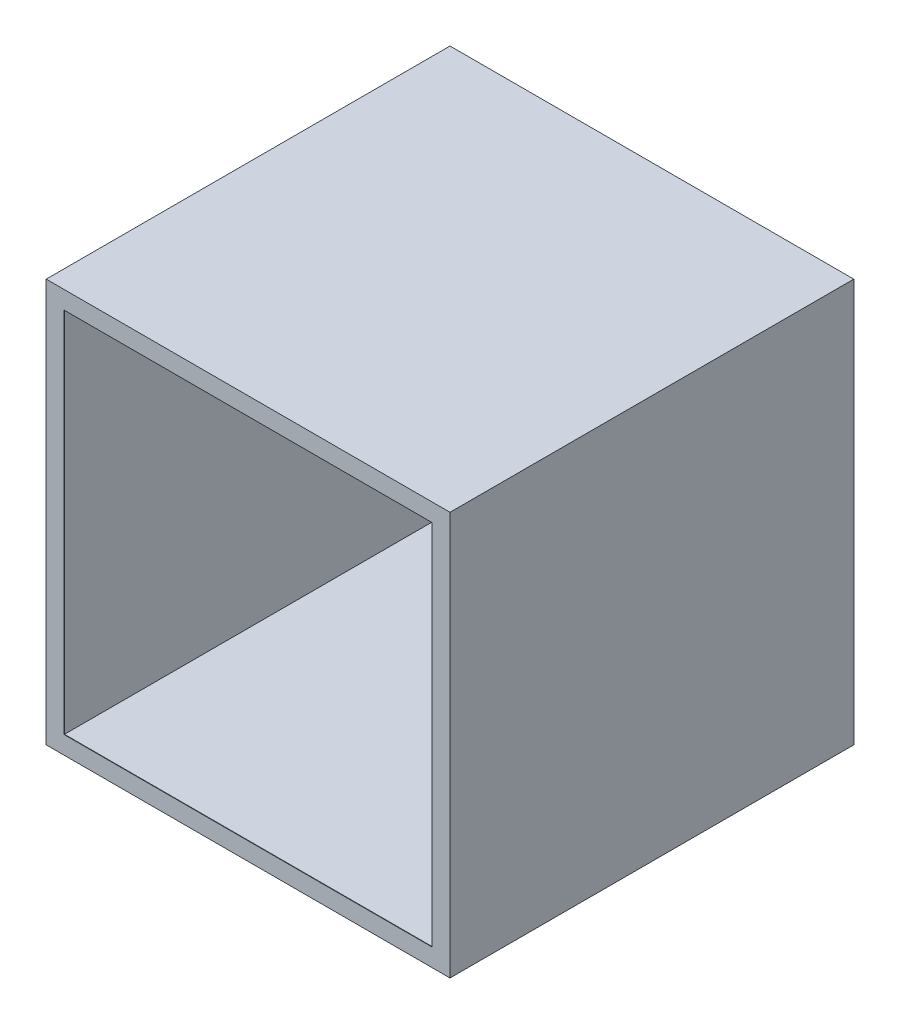
SolidWorks part; units mm, degrees
ref_plane "Front" through (0, 0, 0) normal (0, 0, 1) x (1, 0, 0)
ref_plane "Top" through (0, 0, 0) normal (0, 1, 0) x (1, 0, 0)
ref_plane "Right" through (0, 0, 0) normal (1, 0, 0) x (0, 0, -1)
sketch "Sketch1" plane through (0, 0, 0) normal (0, 1, 0) x (1, 0, 0)
  line L1 (-1300, 1300) -> (1300, 1300)
  line L2 (-1300, 1300) -> (-1300, -1300)
  line L3 (-1300, -1300) -> (1300, -1300)
  line L4 (1300, 1300) -> (1300, -1300)
  line L5 (-1300, 1300) -> (1300, -1300) construction
  line L6 (-1300, -1300) -> (1300, 1300) construction
  point P0 (0, 0)
  dimension "D1" = 2600
  dimension "D2" = 2600
extrude "Boss-Extrude1" add sketch "Sketch1" along normal blind 2597
shell "Shell1" thickness 3 removed face at (0, 1298.5, 1300)
sketch "Sketch3" plane through (0, 0, 1300) normal (0, 0, 1) x (1, 0, 0)
  line L0 (-1300, 2597) -> (1300, 0) construction
  line L1 (-1300, 0) -> (1300, 2597) construction
  line L2 (1300, 2597) -> (1300, 0) construction
  line L3 (-1300, 2597) -> (1300, 2597) construction
  line L5 (-1300, 0) -> (1300, 0)
  line L6 (-1300, 0) -> (-1300, 2597)
  line L7 (-1300, 2597) -> (1300, 2597)
  line L8 (1300, 0) -> (1300, 2597)
  line L9 (-1300, 0) -> (1300, 2597) construction
  line L10 (-1300, 2597) -> (1300, 0) construction
  line L11 (-1185, 115) -> (1185, 115)
  line L12 (-1185, 115) -> (-1185, 2482)
  line L13 (-1185, 2482) -> (1185, 2482)
  line L14 (1185, 115) -> (1185, 2482)
  line L15 (-1185, 115) -> (1185, 2482) construction
  line L16 (-1185, 2482) -> (1185, 115) construction
  point P11 (0, 1298.5)
  point P12 (0, 1298.5)
  dimension "D1" = 115
  dimension "D2" = 115
extrude "Boss-Extrude2" add sketch "Sketch3" against normal blind 3
